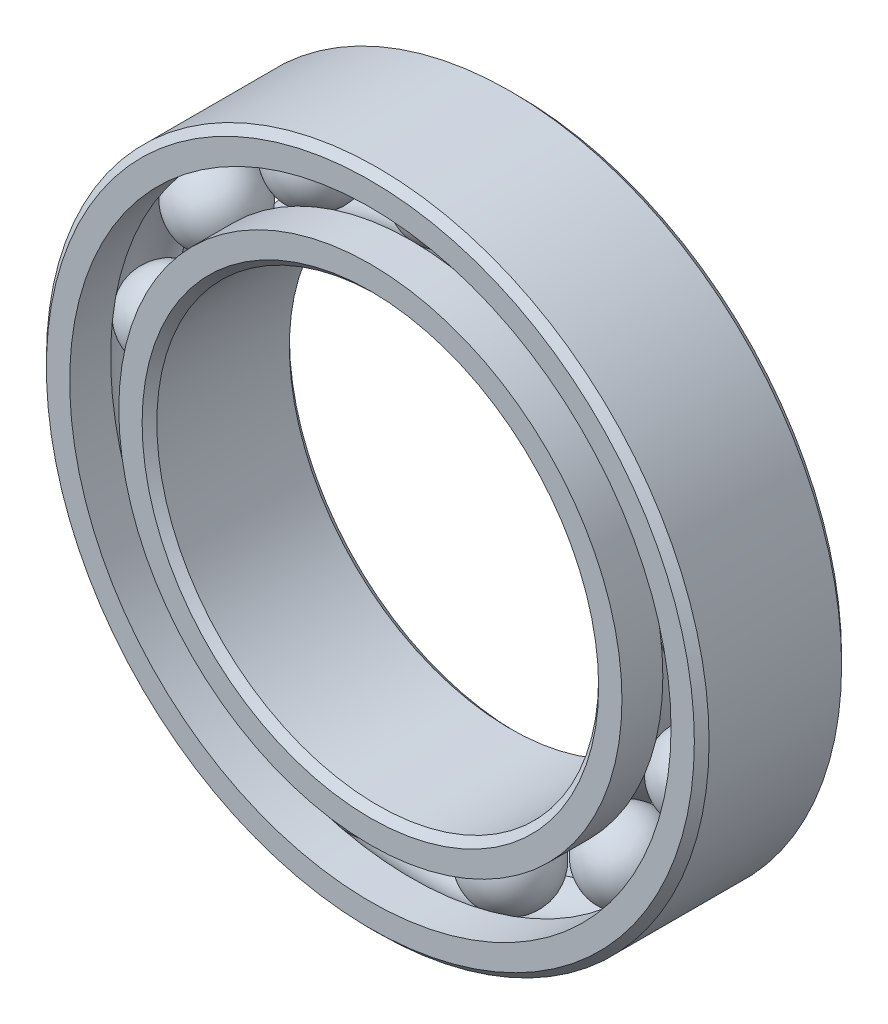
SolidWorks part; units mm, degrees
ref_plane "Front Plane" through (0, 0, 0) normal (0, 0, 1) x (1, 0, 0)
ref_plane "Top Plane" through (0, 0, 0) normal (0, 1, 0) x (1, 0, 0)
ref_plane "Right Plane" through (0, 0, 0) normal (1, 0, 0) x (0, 0, -1)
sketch "Sketch1" plane through (0, 0, 0) normal (0, 0, 1) x (1, 0, 0)
  circle A0 centre (0, 0) radius 9
  circle A1 centre (0, 0) radius 6
  dimension "OD" = 18
  dimension "ID" = 12
  dimension "For Shaft Diameter" = 12
  dimension "For Housing ID" = 18
sketch "Sketch5" plane through (0, 0, 0) normal (1, 0, 0) x (0, 0, -1)
  line L0 (-2, 0) -> (2, 0) construction
  line L1 (0, 9) -> (0, -9) construction
  line L2 (1.8, 9) -> (-1.8, 9)
  line L3 (-1.8, 9) -> (-2, 8.8)
  line L4 (-2, 8.8) -> (-2, 8.1667)
  line L5 (-2, 8.1667) -> (-0.8889, 8.1667)
  line L6 (2, 8.1667) -> (0.8889, 8.1667)
  line L7 (2, 8.8) -> (2, 8.1667)
  line L8 (1.8, 9) -> (2, 8.8)
  line L9 (0, 9) -> (0, 7.5) construction
  line L10 (0, 7.5) -> (0, 6) construction
  line L11 (-1.1111, 7.5) -> (-2, 7.5) construction
  line L12 (1.3651, 6.8587) -> (1.7461, 6.8587) construction
  line L13 (-1.3651, 6.8587) -> (-1.7461, 6.8587) construction
  line L14 (-1.3651, 6.8587) -> (-1.3651, 8.1413) construction
  line L15 (-1.3651, 8.1413) -> (-1.7461, 8.1413) construction
  line L16 (-1.7461, 6.8587) -> (-1.7461, 8.1413) construction
  line L17 (-1.3651, 6.8587) -> (-1.7461, 8.1413) construction
  line L18 (-1.3651, 8.1413) -> (-1.7461, 6.8587) construction
  line L19 (1.7461, 6.8587) -> (1.7461, 8.1413) construction
  line L20 (1.3651, 8.1413) -> (1.7461, 8.1413) construction
  line L21 (1.3651, 6.8587) -> (1.3651, 8.1413) construction
  line L22 (0, 9) -> (0, -9) construction
  arc A0 (-0.8889, 8.1667) -> (0.8889, 8.1667) centre (0, 7.5) cw
  circle A1 centre (0, 7.5) radius 1.1111 construction
  point P14 (0, 6)
  point P15 (-1.5556, 7.5)
  dimension "Width" = 4
  dimension "D1" = 45
  dimension "D2" = 0.2
  dimension "D3" = 1.7778
  dimension "D4" = 0.6667
  dimension "D5" = 0.381
  dimension "D6" = 0.0254
  dimension "D7" = 4
revolve "Revolve1" add sketch "Sketch5" angle 360 about L0
sketch "Sketch3" plane through (0, 0, 0) normal (1, 0, 0) x (0, 0, -1)
  line L0 (-2, 6.8333) -> (-0.8889, 6.8333)
  line L1 (0, 9) -> (0, -9) construction
  line L2 (-2, 8.8) -> (-2, 8.1667) construction
  line L3 (-2, 6.8333) -> (-2, 6.2)
  line L4 (-1.8, 9) -> (-2, 8.8) construction
  line L5 (-2, 6.2) -> (-1.8, 6)
  line L6 (-1.8, 6) -> (1.8, 6)
  line L7 (1.8, 9) -> (1.8, -9) construction
  line L8 (1.8, 6) -> (2, 6.2)
  line L9 (2, -8.8) -> (2, 8.8) construction
  line L10 (2, 6.2) -> (2, 6.8333)
  line L11 (2, 6.8333) -> (0.8889, 6.8333)
  line L13 (1.8, 9) -> (2, 8.8) construction
  arc A0 (0.8889, 8.1667) -> (-0.8889, 8.1667) centre (0, 7.5) ccw construction
  arc A1 (0.8889, 6.8333) -> (-0.8889, 6.8333) centre (0, 7.5) cw
revolve "Revolve3" add sketch "Sketch3" angle 360 about L0
sketch "Sketch4" plane through (0, 0, 0) normal (1, 0, 0) x (0, 0, -1)
  line L0 (-1.1111, 7.5) -> (1.1111, 7.5)
  arc A2 (-1.1111, 7.5) -> (1.1111, 7.5) centre (0, 7.5) cw
  arc A3 (0.8889, 8.1667) -> (-0.8889, 8.1667) centre (0, 7.5) ccw construction
revolve "Revolve4" add sketch "Sketch4" angle 360 about L0
pattern_circular "CirPattern1" count 13 every 27.692 of bodies 104
ref_axis "Center Axis 1" through (0, 0, -1.8) along (0, 0, 1)
equation "\"D2@Sketch5\" = \"Width@Sketch5\" * .05"
equation "\"D3@Sketch5\" = \"Width@Sketch5\" / 2.25"
equation "\"D4@Sketch5\"=((\"OD@Sketch1\"-\"ID@Sketch1\")/2)/4.5"
equation "\"D2@CirPattern1\" = 360/\"Balls@CirPattern1\""
